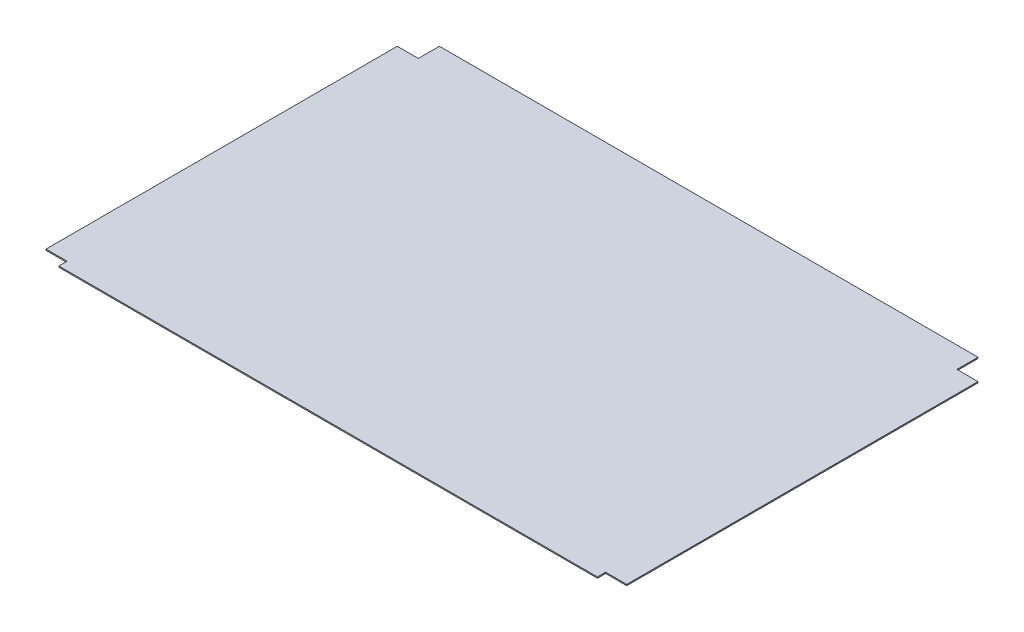
SolidWorks part; units mm, degrees
material "AISI 316 Stainless Steel Sheet (SS)"
ref_plane "Front Plane" through (0, 0, 0) normal (0, 0, 1) x (1, 0, 0)
ref_plane "Top Plane" through (0, 0, 0) normal (0, 1, 0) x (1, 0, 0)
ref_plane "Right Plane" through (0, 0, 0) normal (1, 0, 0) x (0, 0, -1)
sketch "Sketch1" plane through (0, 0, 0) normal (0, 1, 0) x (1, 0, 0)
  line L1 (314.96, -213.36) -> (-314.96, -213.36)
  line L2 (314.96, -213.36) -> (314.96, 213.36)
  line L3 (314.96, 213.36) -> (-314.96, 213.36)
  line L4 (-314.96, -213.36) -> (-314.96, 213.36)
  line L5 (314.96, -213.36) -> (-314.96, 213.36) construction
  line L6 (314.96, 213.36) -> (-314.96, -213.36) construction
  point P0 (0, 0)
  dimension "D1" = 629.92
  dimension "D2" = 426.72
extrude "Extrude1" add sketch "Sketch1" along normal blind 1.27
sketch "Sketch2" plane through (0, 1.27, 0) normal (0, 1, 0) x (1, 0, 0)
  line L1 (-314.96, -213.36) -> (-292.1, -213.36)
  line L2 (-314.96, -213.36) -> (-314.96, -190.5)
  line L3 (-314.96, -190.5) -> (-292.1, -190.5)
  line L4 (-292.1, -213.36) -> (-292.1, -190.5)
  dimension "D1" = 22.86
extrude "Extrude2" cut sketch "Sketch2" against normal through all
mirror "Mirror1" about plane through (0, 0, 0) normal (1, 0, 0) of "Extrude2"
mirror "Mirror2" about plane through (0, 0, 0) normal (0, 0, 1) of "Mirror1"
sketch "Sketch3" plane through (0, 0, 213.36) normal (0, 0, 1) x (1, 0, 0)
  line L4 (292.1, 0) -> (292.1, 1.27)
  line L5 (292.1, 1.27) -> (-292.1, 1.27)
  line L6 (-292.1, 1.27) -> (-292.1, 0)
  line L7 (-292.1, 0) -> (292.1, 0)
  line L8 (292.1, 0) -> (292.1, 1.27)
  line L9 (292.1, 1.27) -> (-292.1, 1.27)
  line L10 (-292.1, 1.27) -> (-292.1, 0)
  line L11 (-292.1, 0) -> (292.1, 0)
  dimension "D1" = 0
extrude "Extrude3" cut sketch "Sketch3" against normal blind 13.97
